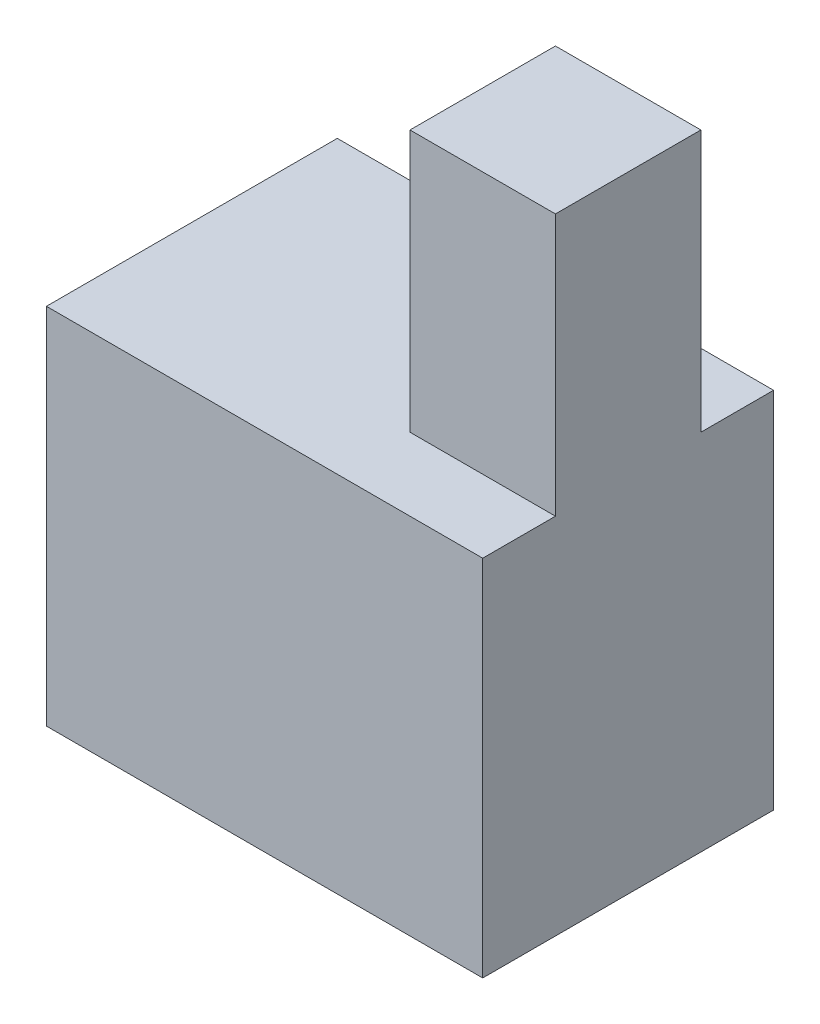
SolidWorks part; units mm, degrees
ref_plane "Front Plane" through (0, 0, 0) normal (0, 0, 1) x (1, 0, 0)
ref_plane "Top Plane" through (0, 0, 0) normal (0, 1, 0) x (1, 0, 0)
ref_plane "Right Plane" through (0, 0, 0) normal (1, 0, 0) x (0, 0, -1)
sketch "Sketch3" plane through (0, 0, 0) normal (0, 0, 1) x (1, 0, 0)
  line L0 (0, 0) -> (0, -5)
  line L1 (0, -5) -> (20, -5)
  line L2 (20, -5) -> (20, -25)
  line L3 (0, 0) -> (20, 0)
  line L4 (20, 0) -> (20, 18)
  line L5 (20, 18) -> (30, 18)
  line L6 (30, 18) -> (30, -25)
  line L7 (30, -25) -> (20, -25)
  dimension "D1" = 20
  dimension "D2" = 20
  dimension "D3" = 20
  dimension "D4" = 5
  dimension "D5" = 10
  dimension "D6" = 43
extrude "Boss-Extrude3" add sketch "Sketch3" along normal blind 10
sketch "Sketch5" plane through (0, 0, 10) normal (0, 0, 1) x (1, 0, 0)
  line L5 (0, 0) -> (30, 0)
  line L6 (0, 0) -> (0, -25)
  line L7 (0, -25) -> (30, -25)
  line L8 (30, 0) -> (30, -25)
extrude "Boss-Extrude5" add sketch "Sketch5" along normal blind 5
sketch "Sketch7" plane through (0, 0, 0) normal (0, 0, -1) x (-1, 0, 0)
  line L0 (-20, 0) -> (-30, 0)
  line L1 (-30, 0) -> (-30, -25)
  line L2 (-30, -25) -> (-20, -25)
  line L3 (-20, -25) -> (-20, -5)
  line L4 (-20, -5) -> (0, -5)
  line L5 (0, -5) -> (0, 0)
  line L6 (0, 0) -> (-20.7589, 0)
  line M8 (0, 0) -> (-20, 0)
  line M11 (-30, 18) -> (-30, -25)
  line M12 (-30, -25) -> (-20, -25)
  line M13 (-20, -25) -> (-20, -5)
  line M14 (-20, -5) -> (0, -5)
  line M15 (0, -5) -> (0, 0)
extrude "Boss-Extrude7" add sketch "Sketch7" along normal blind 5 contours L0 M8 M11 M12 M13 M14 M15 region at (20.7143, -9.6429, 0)
